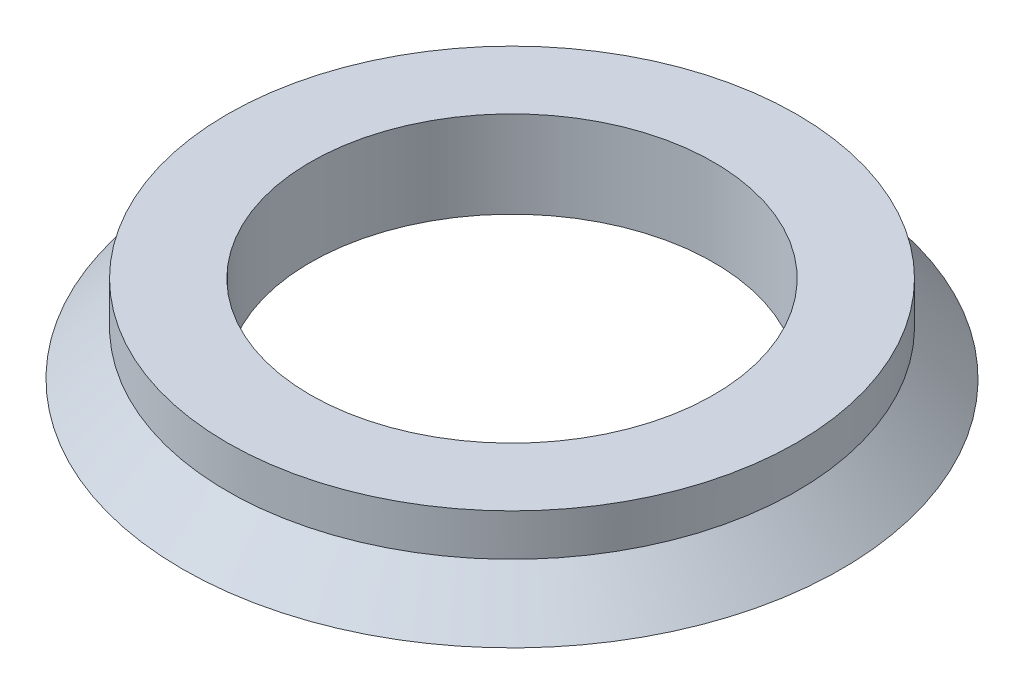
SolidWorks part; units mm, degrees
ref_plane "Front Plane" through (0, 0, 0) normal (0, 0, 1) x (1, 0, 0)
ref_plane "Top Plane" through (0, 0, 0) normal (0, 1, 0) x (1, 0, 0)
ref_plane "Right Plane" through (0, 0, 0) normal (1, 0, 0) x (0, 0, -1)
sketch "Sketch1" plane through (0, 0, 0) normal (0, 1, 0) x (1, 0, 0)
  circle A0 centre (0, 0) radius 11
  circle A1 centre (0, 0) radius 6.731
  dimension "D1" = 22
  dimension "D2" = 13.462
extrude "Boss-Extrude1" add sketch "Sketch1" along normal blind 1.5
chamfer "Chamfer1" distance 1.5 angle 45 1 edges at (0, 1.5, 11)
sketch "Sketch2" plane through (0, 1.5, 0) normal (0, 1, 0) x (1, 0, 0)
  circle A0 centre (0, 0) radius 9.5 construction
  circle A1 centre (0, 0) radius 6.731
  circle A2 centre (0, 0) radius 6.731
  circle A3 centre (0, 0) radius 9.5
  dimension "D1" = 0
extrude "Boss-Extrude2" add sketch "Sketch2" along normal blind 1.4
